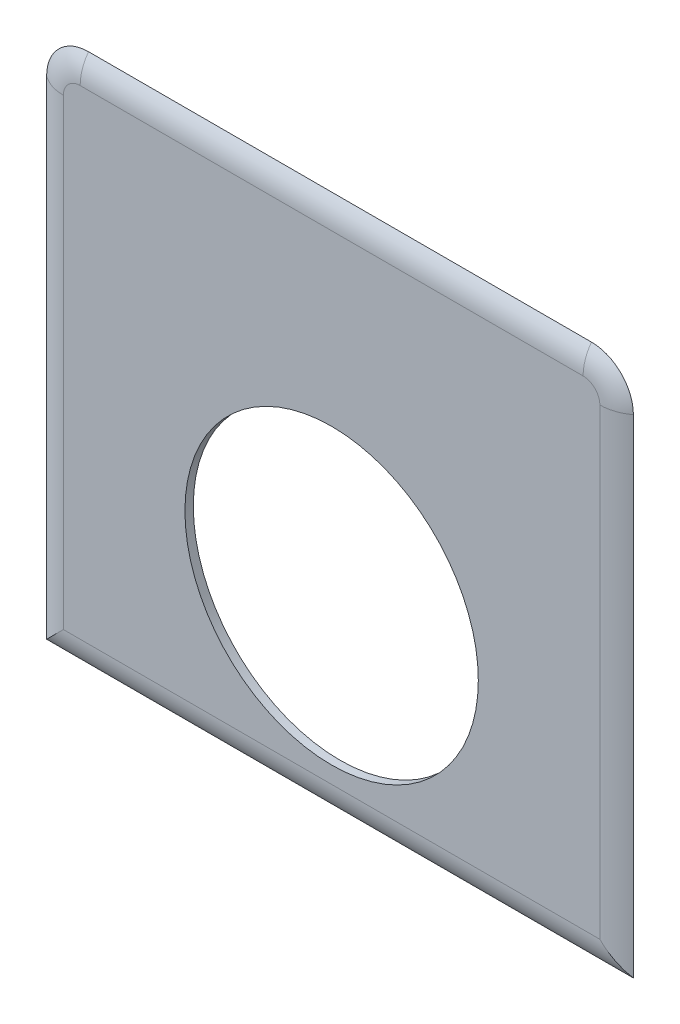
SolidWorks part; units mm, degrees
material "1060 Alloy"
ref_plane "Front Plane" through (0, 0, 0) normal (0, 0, 1) x (1, 0, 0)
ref_plane "Top Plane" through (0, 0, 0) normal (0, 1, 0) x (1, 0, 0)
ref_plane "Right Plane" through (0, 0, 0) normal (1, 0, 0) x (0, 0, -1)
sketch "Sketch1" plane through (0, 0, 0) normal (0, 0, 1) x (1, 0, 0)
  line L0 (88.9, 160.528) -> (88.9, 0) construction
  line L1 (0, 0) -> (177.8, 0)
  line L2 (0, 0) -> (0, 160.528)
  line L3 (0, 160.528) -> (177.8, 160.528)
  line L4 (177.8, 0) -> (177.8, 160.528)
  circle A0 centre (88.9, 57.15) radius 44.45
  point P9 (0, 0)
  dimension "D3" = 88.9
  dimension "D1" = 160.528
  dimension "D2" = 177.8
  dimension "D4" = 57.15
extrude "Boss-Extrude1" add sketch "Sketch1" along normal blind 2.54
fillet "Fillet1" radius 12.7 2 edges at (0, 160.528, 1.27) (177.8, 160.528, 1.27)
fillet "Fillet2" radius 12.7 6 edges at (177.8, 73.914, 2.54) (174.0803, 156.8083, 2.54) (88.9, 160.528, 2.54) (3.7197, 156.8083, 2.54) (0, 73.914, 2.54) (88.9, 0, 2.54)
